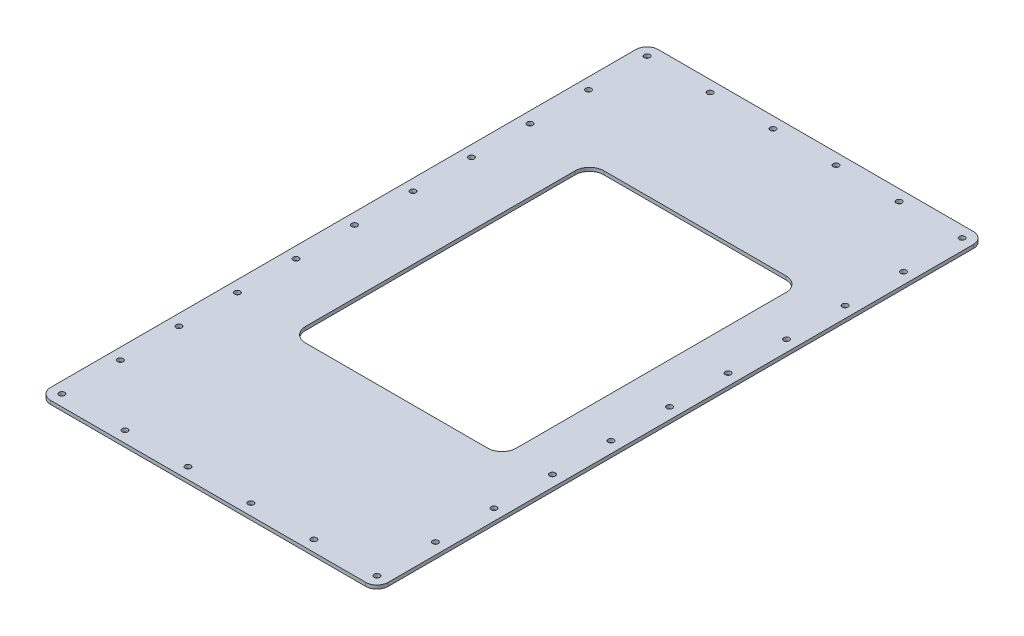
SolidWorks part; units mm, degrees
material "5052-H32"
ref_plane "Front Plane" through (0, 0, 0) normal (0, 0, 1) x (1, 0, 0)
ref_plane "Top Plane" through (0, 0, 0) normal (0, 1, 0) x (1, 0, 0)
ref_plane "Right Plane" through (0, 0, 0) normal (1, 0, 0) x (0, 0, -1)
sketch "Sketch9" plane through (0, 0, 0) normal (0, 1, 0) x (1, 0, 0)
  line L0 (-150, 0) -> (-150, 540)
  line L13 (-150, 540) -> (150, 540)
  line L14 (103.6625, 157.4438) -> (-83.6625, 157.4438)
  line L19 (150, 540) -> (150, 0)
  line L20 (103.6625, 157.4438) -> (103.6625, 422.5563)
  line L21 (103.6625, 422.5563) -> (-83.6625, 422.5563)
  line L22 (-83.6625, 157.4438) -> (-83.6625, 422.5563)
  line L23 (103.6625, 290) -> (-83.6625, 290) construction
  line L24 (10, 422.5562) -> (10, 157.4438) construction
  line L25 (-150, 0) -> (150, 0)
  point P8 (0, 0)
  point P19 (0, 0)
  dimension "D3" = 265.1125
  dimension "D4" = 187.325
  dimension "D1" = 300
  dimension "D2" = 540
  dimension "D6" = 140
  dimension "D5" = 250
extrude "Boss-Extrude7" add sketch "Sketch9" along normal blind 3.175 separate body contours L0 L25 L19 L13 L14 L22 L21 L20 region at (-143.8226, 0, -270)
fillet "Fillet4" radius 10 4 edges at (-150, 1.5875, -540) (150, 1.5875, -540) (-150, 1.5875, 0) (150, 1.5875, 0)
fillet "Fillet5" radius 12.7 4 edges at (-83.6625, 1.5875, -157.4438) (103.6625, 1.5875, -157.4438) (103.6625, 1.5875, -422.5563) (-83.6625, 1.5875, -422.5563)
sketch "Sketch10" plane through (0, 3.175, 0) normal (0, 1, 0) x (1, 0, 0)
  line L0 (-150, 10) -> (-150, 530) construction
  line L1 (-140, 0) -> (140, 0) construction
  circle A0 centre (-140, 10) radius 2.5
  circle A1 centre (-84, 10) radius 2.5
  circle A2 centre (-28, 10) radius 2.5
  circle A3 centre (28, 10) radius 2.5
  circle A4 centre (84, 10) radius 2.5
  circle A5 centre (140, 10) radius 2.5
  circle A10 centre (140, 62) radius 2.5
  circle A15 centre (140, 114) radius 2.5
  circle A20 centre (140, 166) radius 2.5
  circle A25 centre (140, 218) radius 2.5
  circle A30 centre (140, 270) radius 2.5
  circle A35 centre (140, 322) radius 2.5
  circle A40 centre (140, 374) radius 2.5
  circle A45 centre (140, 426) radius 2.5
  circle A50 centre (140, 478) radius 2.5
  circle A51 centre (-84, 530) radius 2.5
  circle A52 centre (-28, 530) radius 2.5
  circle A53 centre (28, 530) radius 2.5
  circle A54 centre (84, 530) radius 2.5
  circle A55 centre (140, 530) radius 2.5
  circle A56 centre (-140, 62) radius 2.5
  circle A57 centre (-140, 114) radius 2.5
  circle A58 centre (-140, 166) radius 2.5
  circle A59 centre (-140, 218) radius 2.5
  circle A60 centre (-140, 270) radius 2.5
  circle A61 centre (-140, 322) radius 2.5
  circle A62 centre (-140, 374) radius 2.5
  circle A63 centre (-140, 426) radius 2.5
  circle A64 centre (-140, 478) radius 2.5
  circle A65 centre (-140, 530) radius 2.5
  circle A66 centre (-84, 62) radius 2.5 [skipped]
  circle A67 centre (-28, 62) radius 2.5 [skipped]
  circle A68 centre (28, 62) radius 2.5 [skipped]
  circle A69 centre (84, 62) radius 2.5 [skipped]
  circle A70 centre (-84, 114) radius 2.5 [skipped]
  circle A71 centre (-28, 114) radius 2.5 [skipped]
  circle A72 centre (28, 114) radius 2.5 [skipped]
  circle A73 centre (84, 114) radius 2.5 [skipped]
  circle A74 centre (-84, 166) radius 2.5 [skipped]
  circle A75 centre (-28, 166) radius 2.5 [skipped]
  circle A76 centre (28, 166) radius 2.5 [skipped]
  circle A77 centre (84, 166) radius 2.5 [skipped]
  circle A78 centre (-84, 218) radius 2.5 [skipped]
  circle A79 centre (-28, 218) radius 2.5 [skipped]
  circle A80 centre (28, 218) radius 2.5 [skipped]
  circle A81 centre (84, 218) radius 2.5 [skipped]
  circle A82 centre (-84, 270) radius 2.5 [skipped]
  circle A83 centre (-28, 270) radius 2.5 [skipped]
  circle A84 centre (28, 270) radius 2.5 [skipped]
  circle A85 centre (84, 270) radius 2.5 [skipped]
  circle A86 centre (-84, 322) radius 2.5 [skipped]
  circle A87 centre (-28, 322) radius 2.5 [skipped]
  circle A88 centre (28, 322) radius 2.5 [skipped]
  circle A89 centre (84, 322) radius 2.5 [skipped]
  circle A90 centre (-84, 374) radius 2.5 [skipped]
  circle A91 centre (-28, 374) radius 2.5 [skipped]
  circle A92 centre (28, 374) radius 2.5 [skipped]
  circle A93 centre (84, 374) radius 2.5 [skipped]
  circle A94 centre (-84, 426) radius 2.5 [skipped]
  circle A95 centre (-28, 426) radius 2.5 [skipped]
  circle A96 centre (28, 426) radius 2.5 [skipped]
  circle A97 centre (84, 426) radius 2.5 [skipped]
  circle A98 centre (-84, 478) radius 2.5 [skipped]
  circle A99 centre (-28, 478) radius 2.5 [skipped]
  circle A100 centre (28, 478) radius 2.5 [skipped]
  circle A101 centre (84, 478) radius 2.5 [skipped]
  dimension "D1" = 5
  dimension "D2" = 10
  dimension "D6" = 52
  dimension "D7" = 56
  dimension "D4" = 6
  dimension "D5" = 11
extrude "Cut-Extrude1" cut sketch "Sketch10" against normal up to next (3.175 mm away)
equation "\"W\"= 260"
equation "\"L\"= 500"
equation "\"Offset\"= 20"
equation "\"H\"= 110"
equation "\"Compartment Width\"= 90"
equation "\"T\"= 4.7625 * 2 / 3"
equation "\"Inside Fillet Radius\"= 10"
equation "\"Hole\"=15"
equation "\"Wheel to Wall\"= 40"
equation "\"D1@Sketch9\"=\"W\"+40"
equation "\"D2@Sketch9\"=\"L\"+40"
equation "\"D6@Sketch10\"=(\"L\"+20)/10"
equation "\"D7@Sketch10\"=(\"W\"+20)/5"
equation "\"D5@Sketch9\"=(\"L\"/2+20)-\"Offset\""
